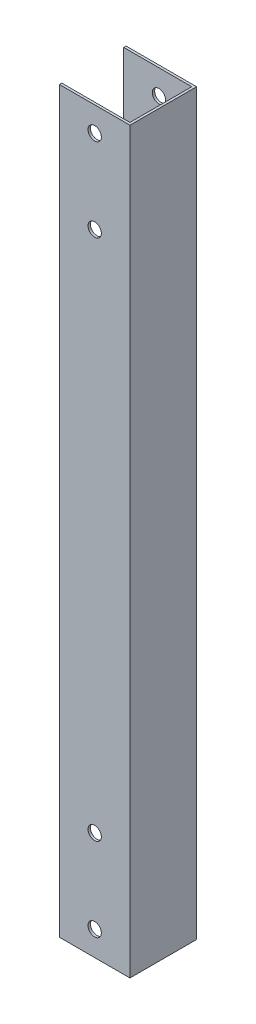
SolidWorks part; units mm, degrees
ref_plane "Front Plane" through (0, 0, 0) normal (0, 0, 1) x (1, 0, 0)
ref_plane "Top Plane" through (0, 0, 0) normal (0, 1, 0) x (1, 0, 0)
ref_plane "Right Plane" through (0, 0, 0) normal (1, 0, 0) x (0, 0, -1)
sketch "Sketch1" plane through (0, 0, 0) normal (0, 1, 0) x (1, 0, 0)
  line L1 (-12.7, 12) -> (12.7, 12)
  line L2 (-12.7, 12) -> (-12.7, -12)
  line L3 (-12.7, -12) -> (12.7, -12)
  line L4 (12.7, 12) -> (12.7, -12)
  line L5 (-12.7, 12) -> (12.7, -12) construction
  line L6 (-12.7, -12) -> (12.7, 12) construction
  point P0 (0, 0)
  dimension "D1" = 24
  dimension "D2" = 25.4
extrude "Boss-Extrude1" add sketch "Sketch1" along normal blind 133 and the other way blind 133
sketch "Sketch2" plane through (0, 0, 0) normal (0, 1, 0) x (1, 0, 0)
  line L0 (-14.16, 11.14) -> (11.84, 11.14)
  line L1 (11.84, 11.14) -> (11.84, -11.14)
  line L2 (11.84, -11.14) -> (-14.16, -11.14)
  line L3 (-14.16, -11.14) -> (-14.16, 11.14)
  line L4 (12.7, 12) -> (-12.7, 12) construction
  line L5 (12.7, -12) -> (12.7, 12) construction
  line L6 (-12.7, -12) -> (12.7, -12) construction
  dimension "D1" = 0.86
  dimension "D2" = 0.86
  dimension "D3" = 0.86
  dimension "D4" = 26
extrude "Cut-Extrude1" cut sketch "Sketch2" against normal blind 150 and the other way blind 150
sketch "Sketch3" plane through (0, 0, 0) normal (0, 0, 1) x (1, 0, 0)
  line L0 (0, 124.125) -> (0, -124.125) construction
  circle A0 centre (0, 124.125) radius 2.4
  circle A1 centre (0, 94.125) radius 2.4
  circle A2 centre (0, -124.125) radius 2.4
  circle A3 centre (0, -94.125) radius 2.4
  dimension "D2" = 4.8
  dimension "D1" = 248.25
  dimension "D3" = 30
  dimension "D4" = 30
extrude "Cut-Extrude2" cut sketch "Sketch3" against normal blind 150 and the other way blind 150
